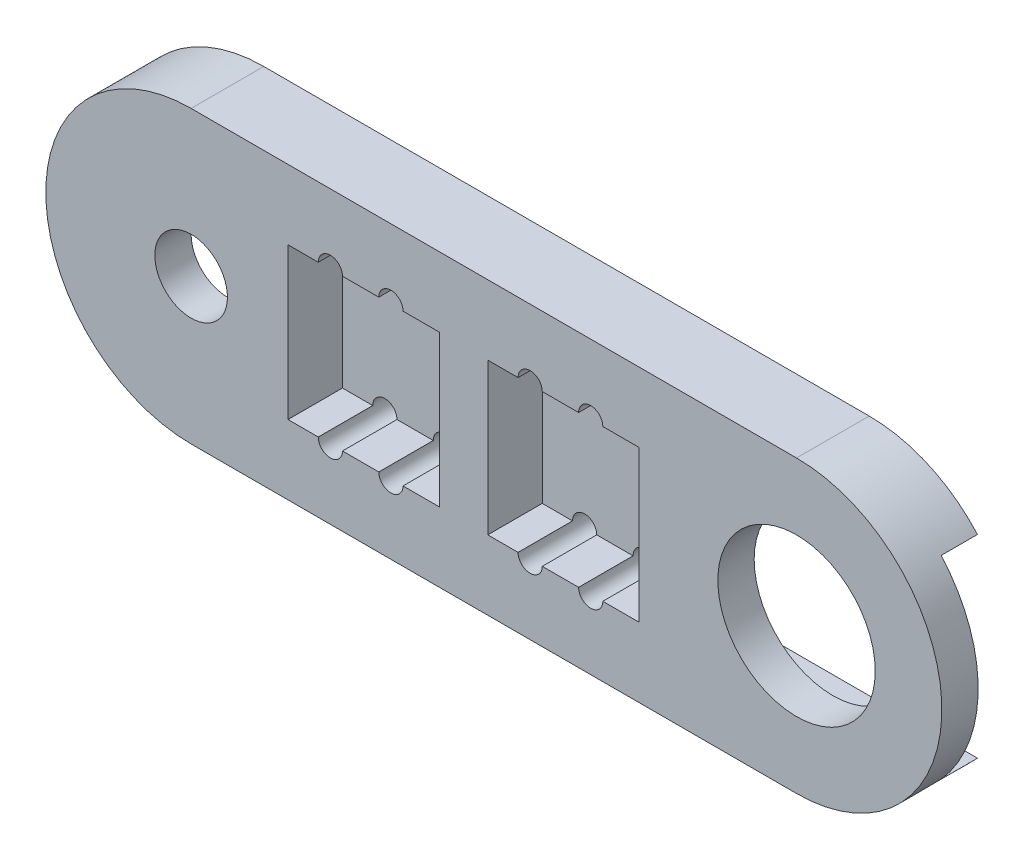
SolidWorks part; units mm, degrees
ref_plane "Спереди" through (0, 0, 0) normal (0, 0, 1) x (1, 0, 0)
ref_plane "Сверху" through (0, 0, 0) normal (0, 1, 0) x (1, 0, 0)
ref_plane "Справа" through (0, 0, 0) normal (1, 0, 0) x (0, 0, -1)
other "Configuration Table"
sketch "Эскиз1" plane through (0, 0, 0) normal (0, 0, 1) x (1, 0, 0)
  line L0 (0, -9.9) -> (50, -9.9) construction
  line L1 (0, 0) -> (50, 0)
  line L3 (0, -19.8) -> (50, -19.8)
  arc A4 (50, -19.8) -> (50, 0) centre (50, -9.9) ccw
  arc A5 (0, 0) -> (0, -19.8) centre (0, -9.9) ccw
  point P9 (0, 0)
  point P12 (50, -19.8)
  point P15 (50, 0)
  dimension "D1" = 19.8
extrude "Бобышка-Вытянуть1" add sketch "Эскиз1" along normal blind 6
sketch "Эскиз4" plane through (0, 0, 6) normal (0, 0, 1) x (1, 0, 0)
  line L1 (8, -3.65) -> (20.5, -3.65)
  line L2 (8, -3.65) -> (8, -16.15)
  line L3 (8, -16.15) -> (20.5, -16.15)
  line L4 (20.5, -3.65) -> (20.5, -16.15)
  line L5 (24.5, -3.65) -> (37, -3.65)
  line L6 (24.5, -3.65) -> (24.5, -16.15)
  line L7 (24.5, -16.15) -> (37, -16.15)
  line L8 (37, -3.65) -> (37, -16.15)
  line L11 (-9.9, -9.9) -> (59.9, -9.9) construction
  arc A0 (0, 0) -> (0, -19.8) centre (0, -9.9) ccw construction
  arc A1 (50, -19.8) -> (50, 0) centre (50, -9.9) ccw construction
  dimension "D1" = 12.5
  dimension "D2" = 12.5
  dimension "D3" = 12.5
  dimension "D4" = 12.5
  dimension "D5" = 6.25
  dimension "D6" = 8
  dimension "D7" = 4
extrude "Вырез-Вытянуть1" cut sketch "Эскиз4" against normal blind 4.5
sketch "Эскиз5" plane through (0, 0, 6) normal (0, 0, 1) x (1, 0, 0)
  circle A0 centre (0, -9.9) radius 3
  circle A1 centre (50, -9.9) radius 6.5
  dimension "D1" = 6
  dimension "D2" = 13
  dimension "D3" = 50
extrude "Вырез-Вытянуть2" cut sketch "Эскиз5" against normal through all
sketch "Эскиз6" plane through (0, 0, 6) normal (0, 0, 1) x (1, 0, 0)
  line L0 (20.5, -3.65) -> (8, -3.65) construction
  line L1 (37, -3.65) -> (24.5, -3.65) construction
  line L2 (8, -16.15) -> (20.5, -16.15) construction
  line L3 (24.5, -16.15) -> (37, -16.15) construction
  line L4 (8, -3.65) -> (8, -16.15) construction
  line L6 (24.5, -3.65) -> (24.5, -16.15) construction
  circle A0 centre (11.5, -3.65) radius 1
  circle A1 centre (16.5, -3.65) radius 1
  circle A2 centre (28, -3.65) radius 1
  circle A3 centre (33, -3.65) radius 1
  circle A4 centre (11.5, -16.15) radius 1
  circle A5 centre (16.5, -16.15) radius 1
  circle A6 centre (28, -16.15) radius 1
  circle A7 centre (33, -16.15) radius 1
  dimension "D1" = 2
  dimension "D2" = 3.5
  dimension "D3" = 5
  dimension "D4" = 3.5
  dimension "D5" = 5
extrude "Вырез-Вытянуть3" cut sketch "Эскиз6" against normal through all
sketch "Эскиз7" plane through (0, 0, 6) normal (0, 0, 1) x (1, 0, 0)
  circle A0 centre (40, -1.9) radius 1.55
  circle A1 centre (40, -17.9) radius 1.55
  circle A2 centre (7, -1.9) radius 1.55
  circle A3 centre (7, -17.9) radius 1.55
  circle A4 centre (0, -9.9) radius 3 construction
  circle A5 centre (50, -9.9) radius 6.5 construction
  dimension "D1" = 3.1
  dimension "D2" = 7
  dimension "D3" = 10
  dimension "D4" = 8
  dimension "D5" = 8
extrude "Вырез-Вытянуть4" [suppressed] cut sketch "Эскиз7" against normal blind 10
sketch "Эскиз8" plane through (0, 0, 6) normal (0, 0, 1) x (1, 0, 0)
  line L0 (0, -9.9) -> (50, -9.9) construction
  line L1 (0, -0.2094) -> (50, -0.2094)
  line L2 (0, -19.5906) -> (50, -19.5906)
  line L3 (0, -9.9) -> (50, -9.9) construction
  line L4 (0, 2.1) -> (50, 2.1)
  line L5 (0, -21.9) -> (50, -21.9)
  arc A0 (0, -0.2094) -> (0, -19.5906) centre (0, -9.9) ccw
  arc A1 (50, -19.5906) -> (50, -0.2094) centre (50, -9.9) ccw
  arc A2 (0, 2.1) -> (0, -21.9) centre (0, -9.9) ccw
  arc A3 (50, -21.9) -> (50, 2.1) centre (50, -9.9) ccw
  point P4 (25, -9.9)
  point P9 (25, -9.9)
  dimension "D1" = 24
extrude "Бобышка-Вытянуть2" add sketch "Эскиз8" against normal blind 6
sketch "Эскиз9" plane through (0, 0, 0) normal (0, 0, -1) x (-1, 0, 0)
  line L1 (-6, -3.9) -> (6, -3.9)
  line L2 (-6, -3.9) -> (-6, -15.9)
  line L3 (-6, -15.9) -> (6, -15.9)
  line L4 (6, -3.9) -> (6, -15.9)
  line L5 (-6, -3.9) -> (6, -15.9) construction
  line L6 (-6, -15.9) -> (6, -3.9) construction
  line L7 (-65, -1.9) -> (-35, -1.9)
  line L8 (-65, -1.9) -> (-65, -17.9)
  line L9 (-65, -17.9) -> (-35, -17.9)
  line L10 (-35, -1.9) -> (-35, -17.9)
  line L11 (-65, -1.9) -> (-35, -17.9) construction
  line L12 (-65, -17.9) -> (-35, -1.9) construction
  point P0 (0, -9.9)
  point P6 (-50, -9.9)
  dimension "D1" = 12
  dimension "D2" = 12
  dimension "D3" = 16
  dimension "D4" = 30
extrude "Вырез-Вытянуть5" cut sketch "Эскиз9" against normal blind 3
